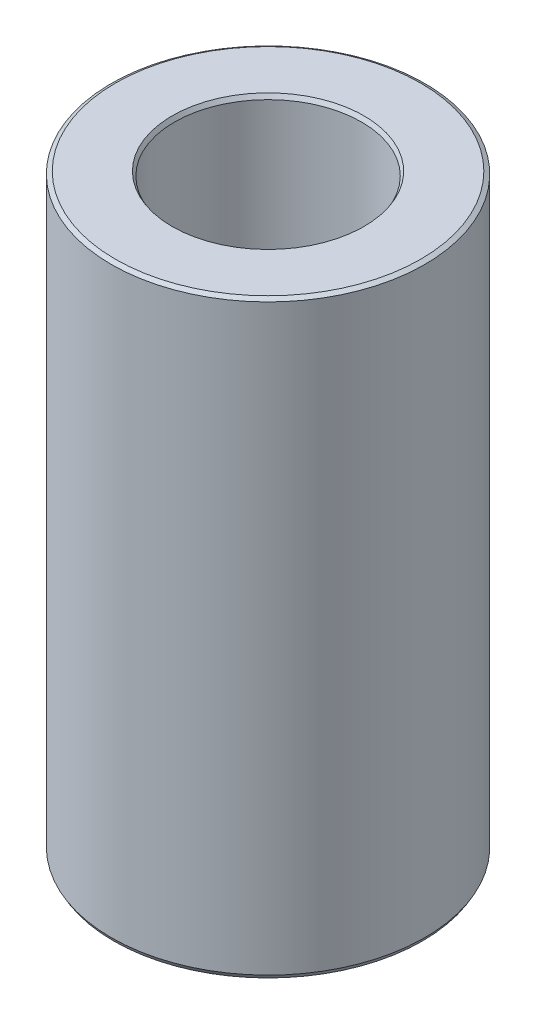
SolidWorks part; units mm, degrees
ref_plane "Front Plane" through (0, 0, 0) normal (0, 0, 1) x (1, 0, 0)
ref_plane "Top Plane" through (0, 0, 0) normal (0, 1, 0) x (1, 0, 0)
ref_plane "Right Plane" through (0, 0, 0) normal (1, 0, 0) x (0, 0, -1)
sketch "Sketch1" plane through (0, 0, 0) normal (0, 1, 0) x (1, 0, 0)
  circle A0 centre (0, 0) radius 45
  dimension "SLEEVE_OD" = 90
extrude "Boss-Extrude1" add sketch "Sketch1" along normal blind 169.2296
sketch "Sketch2" plane through (0, 0, 0) normal (0, 1, 0) x (1, 0, 0)
  circle A0 centre (0, 0) radius 26.8433
  dimension "BORE_D" = 53.6867
extrude "Cut-Extrude1" cut sketch "Sketch2" along normal through all
chamfer "Chamfer1" distance 0.6915 angle 60 4 edges at (0, 169.2296, 26.8433) (0, 0, 26.8433) (0, 0, 45) (0, 169.2296, 45) first distance on face at (0, 169.2296, 26.8433) first distance on face at (0, 0, 26.8433) first distance on face at (0, 169.2296, 45)
